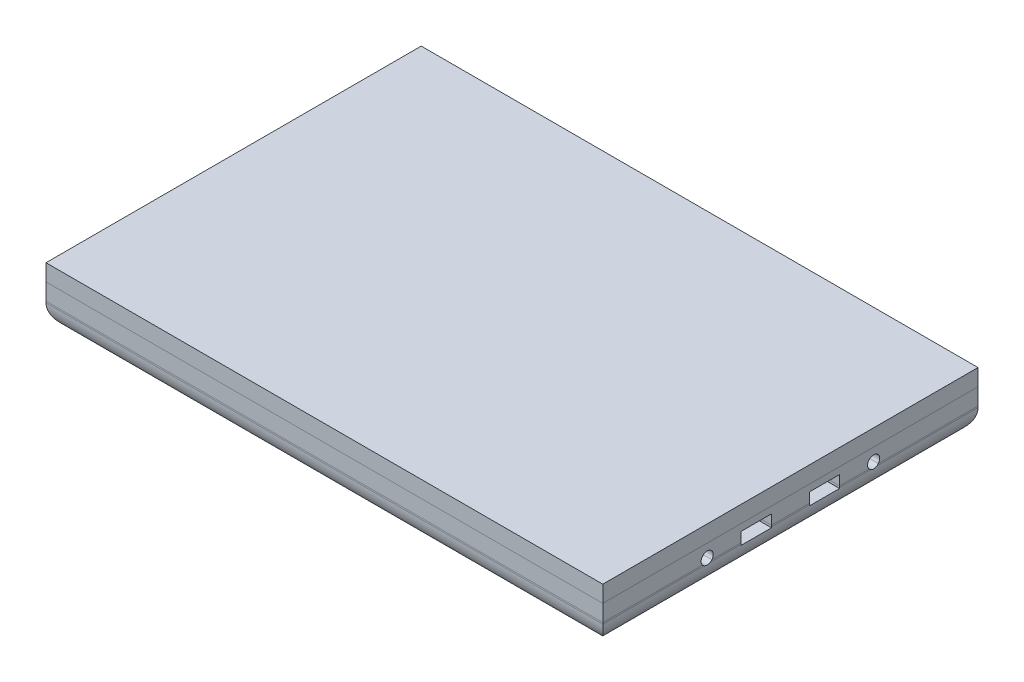
SolidWorks part; units mm, degrees
ref_plane "Front Plane" through (0, 0, 0) normal (0, 0, 1) x (1, 0, 0)
ref_plane "Top Plane" through (0, 0, 0) normal (0, 1, 0) x (1, 0, 0)
ref_plane "Right Plane" through (0, 0, 0) normal (1, 0, 0) x (0, 0, -1)
sketch "Sketch1" plane through (0, 0, 0) normal (0, 1, 0) x (1, 0, 0)
  line L0 (-92, -62) -> (-92, 62)
  line L1 (-92, -62) -> (92, -62)
  line L2 (-92, 62) -> (92, 62)
  line L3 (92, -62) -> (92, 62)
  line L4 (-92, -62) -> (92, 62) construction
  line L5 (-92, 62) -> (92, -62) construction
  point P1 (0, 0)
  dimension "D1" = 184
  dimension "D2" = 124
extrude "Boss-Extrude1" add sketch "Sketch1" along normal blind 5.5
extrude "Boss-Extrude2" add sketch "Sketch1<2>" against normal blind 5.5 separate body
sketch "Sketch1<2>" plane through (0, 0, 0) normal (0, 1, 0) x (1, 0, 0) same geometry as "Sketch1"
sketch "Sketch2" plane through (0, -5.5, 0) normal (0, -1, 0) x (-1, 0, 0)
  line L1 (-92, 62) -> (92, 62)
  line L2 (-92, 62) -> (-92, -62)
  line L3 (-92, -62) -> (92, -62)
  line L4 (92, 62) -> (92, -62)
extrude "Boss-Extrude3" add sketch "Sketch2" along normal blind 8.5 separate body
fillet "Fillet1" radius 8 4 edges at (92, -14, 0) (0, -14, 62) (-92, -14, 0) (0, -14, -62) type face fillet first side face at (92, -9.75, 0) first side face at (-92, -9.75, 0) first side face at (0, -9.75, -62) first side face at (0, -9.75, 62) second side face at (0, -14, 0)
sketch "Sketch3" plane through (92, 0, 0) normal (1, 0, 0) x (0, 0, -1)
  line L0 (0, 0) -> (0, -4.25)
  line L1 (-62, 0) -> (62, 0) construction
  line L2 (-16.25, -6.25) -> (-6.25, -6.25)
  line L3 (-16.25, -6.25) -> (-16.25, -2.25)
  line L4 (-6.25, -6.25) -> (-6.25, -2.25)
  line L5 (-16.25, -2.25) -> (-6.25, -2.25)
  line L6 (-16.25, -6.25) -> (-6.25, -2.25) construction
  line L7 (-6.25, -6.25) -> (-16.25, -2.25) construction
  circle A0 centre (0, -4.25) radius 11.25
  circle A1 centre (0, -4.25) radius 27.5
  circle A2 centre (-27.5, -4.25) radius 2
  point P9 (-11.25, -4.25)
  dimension "D2" = 22.5
  dimension "D3" = 55
  dimension "D4" = 10
  dimension "D1" = 4.25
  dimension "D5" = 4
extrude "Cut-Extrude1" cut sketch "Sketch3" against normal blind 8.5 contours L5 A0 L2 L4 | A0 L5 L3 L2 | A2 region at (92, -4.25, 13.7199) region at (92, -4.25, 8.7205)
mirror "Mirror1" about plane through (0, 0, 0) normal (0, 0, 1) of "Cut-Extrude1"
ref_axis "Axis1" through (0, 6.475, 0) along (0, -1, 0)
